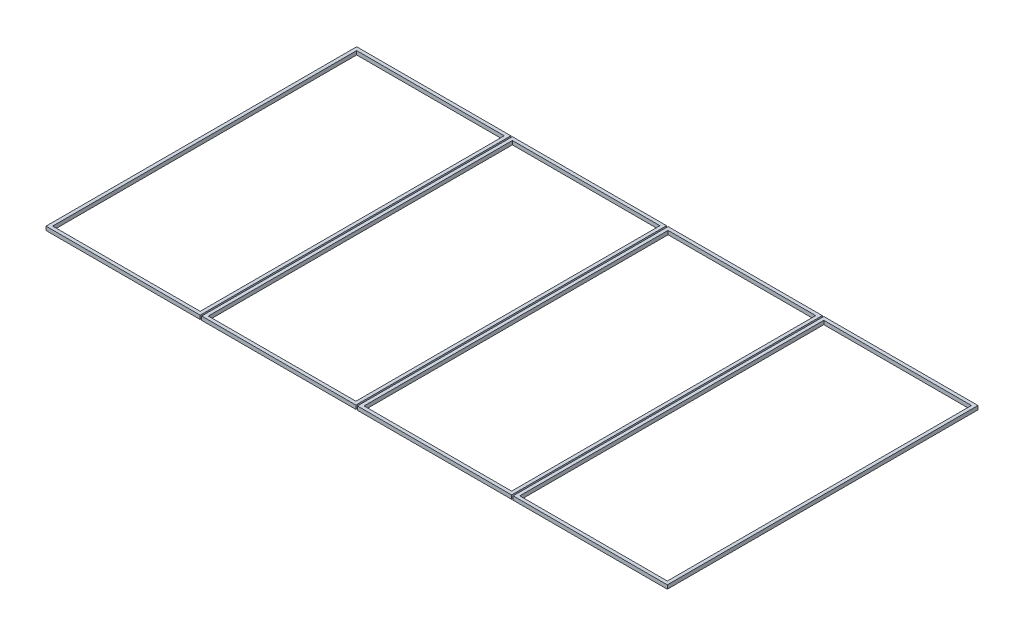
SolidWorks part; units mm, degrees
ref_plane "Front Plane" through (0, 0, 0) normal (0, 0, 1) x (1, 0, 0)
ref_plane "Top Plane" through (0, 0, 0) normal (0, 1, 0) x (1, 0, 0)
ref_plane "Right Plane" through (0, 0, 0) normal (1, 0, 0) x (0, 0, -1)
sketch "Sketch1" plane through (0, 0, 0) normal (0, 1, 0) x (1, 0, 0)
  line L2 (0, 0) -> (0, 1220)
  line L3 (0, 1220) -> (605.5, 1220)
  line L4 (2440, 0) -> (2440, 1220)
  line L5 (13, 1207) -> (592.5, 1207)
  line L10 (13, 1207) -> (13, 13)
  line L11 (13, 13) -> (592.5, 13)
  line L12 (592.5, 1207) -> (592.5, 13)
  line L13 (624.5, 1207) -> (1204, 1207)
  line L14 (624.5, 1207) -> (624.5, 13)
  line L15 (624.5, 13) -> (1204, 13)
  line L16 (1204, 1207) -> (1204, 13)
  line L17 (0, 0) -> (13, 0)
  line L18 (13, 0) -> (592.5, 0)
  line L19 (592.5, 0) -> (605.5, 0)
  line L20 (624.5, 0) -> (1204, 0)
  line L21 (1236, 13) -> (1815.5, 13)
  line L22 (1236, 13) -> (1236, 1207)
  line L23 (1236, 1207) -> (1815.5, 1207)
  line L24 (1815.5, 13) -> (1815.5, 1207)
  line L25 (605.5, 0) -> (611.5, 0) construction
  line L26 (1236, 0) -> (1815.5, 0)
  line L27 (611.5, 0) -> (624.5, 0)
  line L28 (1847.5, 0) -> (2427, 0)
  line L29 (2427, 0) -> (2440, 0)
  line L31 (1847.5, 1207) -> (2427, 1207)
  line L32 (1847.5, 1207) -> (1847.5, 13)
  line L33 (1847.5, 13) -> (2427, 13)
  line L34 (2427, 1207) -> (2427, 13)
  line L48 (1204, 0) -> (1217, 0)
  line L49 (1217, 0) -> (1223, 0) construction
  line L50 (1223, 0) -> (1236, 0)
  line L51 (1815.5, 0) -> (1828.5, 0)
  line L52 (1828.5, 0) -> (1834.5, 0) construction
  line L53 (1834.5, 0) -> (1847.5, 0)
  line L54 (605.5, 0) -> (605.5, 1220)
  line L55 (611.5, 0) -> (611.5, 1220)
  line L56 (1217, 0) -> (1217, 1220)
  line L57 (1223, 0) -> (1223, 1220)
  line L58 (1828.5, 0) -> (1828.5, 1220)
  line L59 (1834.5, 0) -> (1834.5, 1220)
  line L60 (611.5, 1220) -> (1217, 1220)
  line L61 (605.5, 1220) -> (611.5, 1220) construction
  line L62 (1223, 1220) -> (1828.5, 1220)
  line L63 (1217, 1220) -> (1223, 1220) construction
  line L64 (1834.5, 1220) -> (2440, 1220)
  line L65 (1828.5, 1220) -> (1834.5, 1220) construction
  line L66 (19.5, 1200.5) -> (586, 1200.5) construction
  line L67 (586, 1200.5) -> (586, 19.5) construction
  line L68 (19.5, 19.5) -> (586, 19.5) construction
  line L69 (19.5, 1200.5) -> (19.5, 19.5) construction
  dimension "D1" = 2440
  dimension "D2" = 1220
  dimension "D8" = 13
  dimension "D3" = 13
  dimension "D4" = 13
  dimension "D9" = 13
  dimension "D12" = 6
  dimension "D7" = 611.5
  dimension "D10" = 566.5
  dimension "D5" = 1181
  dimension "D6" = 6.5
extrude "Boss.-Extru.1" add sketch "Sketch1" along normal blind 15
equation "\"D12@Sketch1\"=\"tool_diameter\""
equation "\"tool_diameter\"=6"
equation "\"material_thickness\"=15"
equation "\"clearance_tight\"=0.1"
equation "\"D1@Boss.-Extru.1\"=\"material_thickness\""
equation "\"big_holes\"=56"
equation "\"tab_thickness\" = 25"
equation "\"tab_height\" = 3"
equation "\"D6@Sketch1\"=\"tool_diameter\" + \"clearance_loose\""
equation "\"D5@Extrude-Thin1\"=\"tab_thickness\""
equation "\"D1@Extrude-Thin1\"=\"tab_height\""
equation "\"clearance_loose\"=0.5"
equation "\"small_holes\"=10"
equation "\"string\"= 2 * \"tool_diameter\" / 2 * cos ( 45deg )"
equation "\"angle\"= IIF ( \"string\" < \"limit\" , 45 , ( 180 - 2 * arcsin ( \"ThicknessVStool_dia\" ) ) / 2 )"
equation "\"limit\"= \"material_thickness\" / 2 * 9 / 10"
equation "\"ThicknessVStool_dia\"= IIF ( \"limit\" / \"tool_diameter\" > 1 , 1 , \"limit\" / \"tool_diameter\" )"
